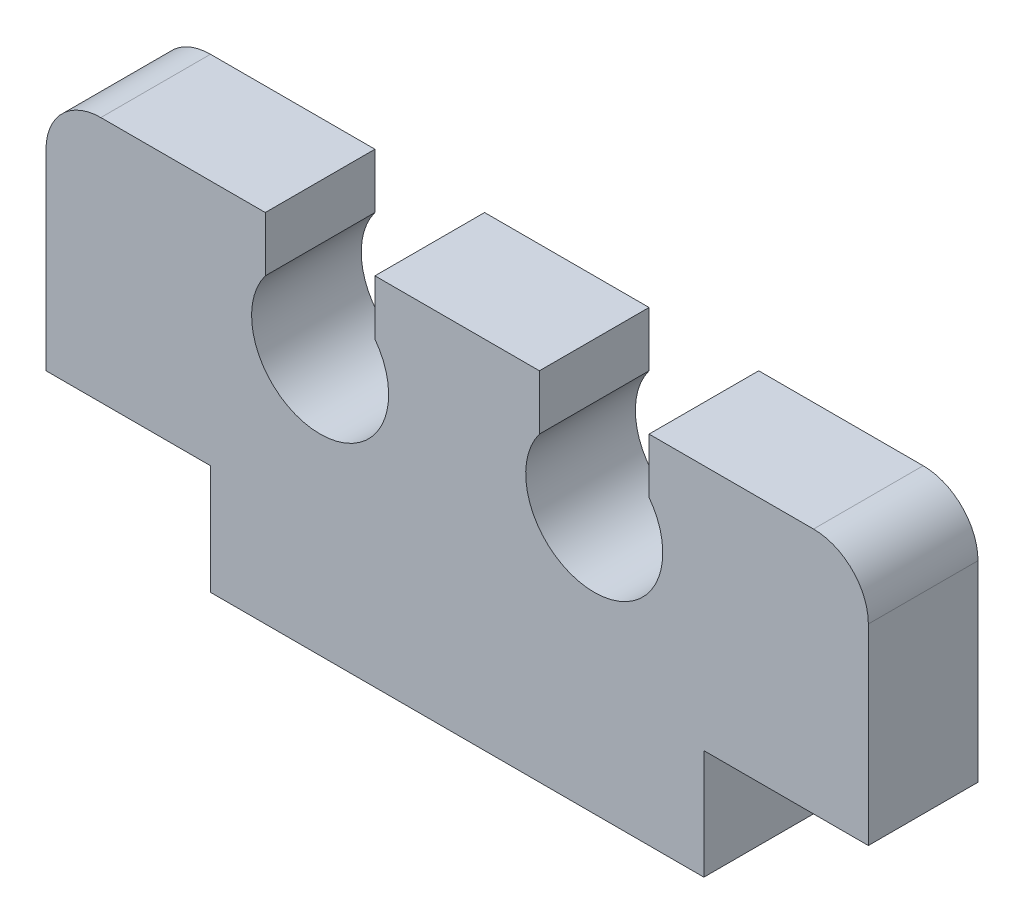
SolidWorks part; units mm, degrees
ref_plane "Front Plane" through (0, 0, 0) normal (0, 0, 1) x (1, 0, 0)
ref_plane "Top Plane" through (0, 0, 0) normal (0, 1, 0) x (1, 0, 0)
ref_plane "Right Plane" through (0, 0, 0) normal (1, 0, 0) x (0, 0, -1)
sketch "Sketch1" plane through (0, 0, 0) normal (0, 0, 1) x (1, 0, 0)
  line L14 (-4.5, 0) -> (4.5, 0)
  line L15 (-4.5, 0) -> (-4.5, 2)
  line L16 (-4.5, 2) -> (-7.5, 2)
  line L17 (-7.5, 2) -> (-7.5, 6.5)
  line L18 (-7.5, 6.5) -> (-3.5, 6.5)
  line L19 (0, 6.5) -> (0, 0) construction
  line L20 (-3.5, 5.5) -> (-3.5, 6.5)
  line L21 (-1.5, 5.5) -> (-1.5, 6.5)
  line L22 (-1.5, 6.5) -> (1.5, 6.5)
  line L23 (1.5, 5.5) -> (1.5, 6.5)
  line L24 (3.5, 5.5) -> (3.5, 6.5)
  line L25 (7.5, 6.5) -> (3.5, 6.5)
  line L26 (7.5, 2) -> (7.5, 6.5)
  line L27 (4.5, 2) -> (7.5, 2)
  line L28 (4.5, 0) -> (4.5, 2)
  arc A4 (-3.5, 5.5) -> (-1.5, 5.5) centre (-2.5, 4.75) ccw
  arc A5 (3.5, 5.5) -> (1.5, 5.5) centre (2.5, 4.75) cw
  dimension "D2" = 2.5
  dimension "D1" = 1.75
  dimension "D3" = 2
  dimension "D4" = 4.5
  dimension "D5" = 7.5
  dimension "D6" = 2
  dimension "D7" = 6.5
  dimension "D8" = 2.5
extrude "Tube Plate MCP Body" add sketch "Sketch1" along normal blind 2
fillet "Tube Plate MCP Contouring" radius 1 2 edges at (7.5, 6.5, 1) (-7.5, 6.5, 1)
equation "\"D7@Sketch1\"=\"rp@Parameters@RobotHandParameters.SLDPRT\" - 2 - \"Tjointp@Parameters@RobotHandParameters.SLDPRT\"/2 + 1.75mm"
